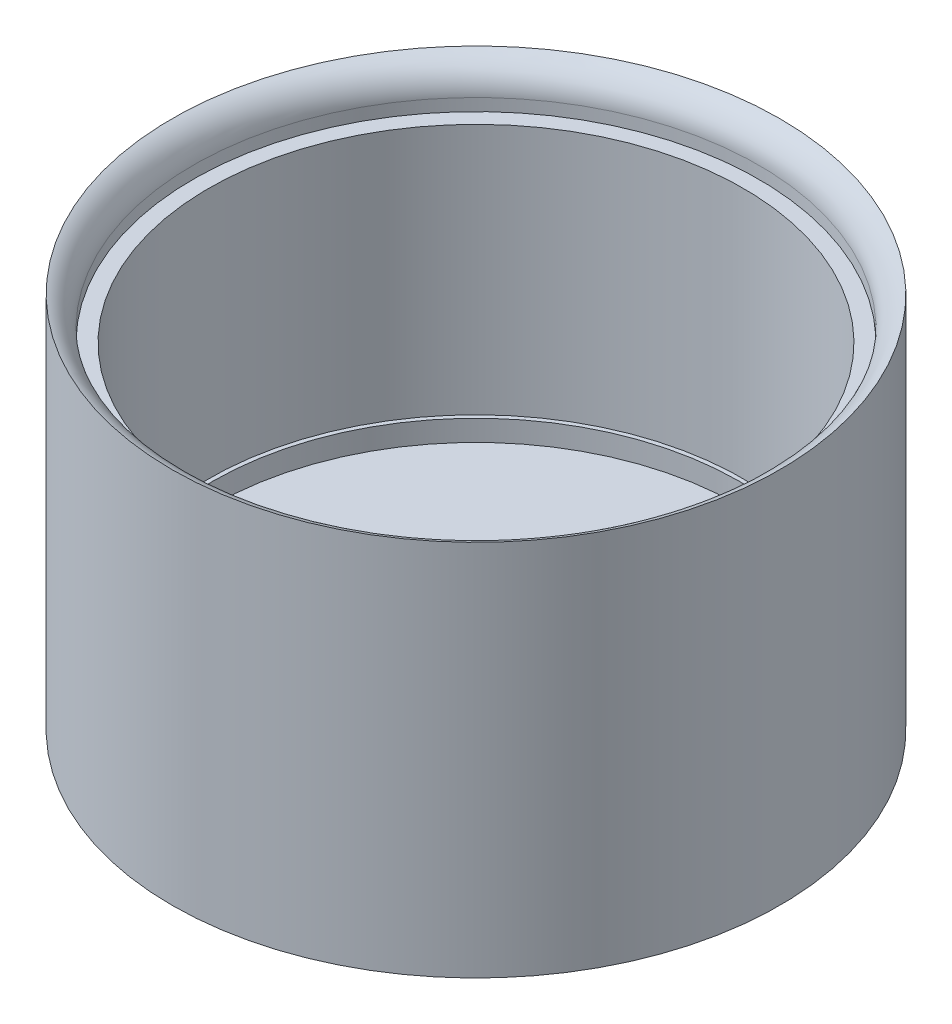
SolidWorks part; units mm, degrees
ref_plane "Alzado" through (0, 0, 0) normal (0, 0, 1) x (1, 0, 0)
ref_plane "Planta" through (0, 0, 0) normal (0, 1, 0) x (1, 0, 0)
ref_plane "Vista lateral" through (0, 0, 0) normal (1, 0, 0) x (0, 0, -1)
sketch "Sketch1" plane through (0, 0, 0) normal (0, 1, 0) x (1, 0, 0)
  circle A0 centre (0, 0) radius 25.5
  circle A1 centre (0, 0) radius 29
  dimension "D1" = 51
  dimension "D2" = 3.5
extrude "Boss-Extrude1" add sketch "Sketch1" along normal blind 30
sketch "Sketch2" plane through (0, 30, 0) normal (0, 1, 0) x (1, 0, 0)
  circle A0 centre (0, 0) radius 25.5
  circle A1 centre (0, 0) radius 26.9839
extrude "Cut-Extrude1" cut sketch "Sketch2" against normal blind 4
fillet "Fillet1" radius 3 1 edges at (0, 30, 26.9839)
sketch "Sketch3" plane through (0, 0, 0) normal (0, -1, 0) x (1, 0, 0)
  circle A0 centre (0, 0) radius 29
extrude "Boss-Extrude2" add sketch "Sketch3" along normal blind 6
sketch "Sketch4" plane through (0, 0, 0) normal (0, 1, 0) x (1, 0, 0)
  circle A2 centre (0, 0) radius 4
  dimension "D1" = 8
extrude "Cut-Extrude2" cut sketch "Sketch4" against normal blind 4.3
sketch "Sketch5" plane through (0, 0, 0) normal (0, 1, 0) x (1, 0, 0)
  circle A0 centre (0, 0) radius 25.5
  circle A1 centre (0, 0) radius 25.1
  dimension "D1" = 51
  dimension "D2" = 0.4
extrude "Boss-Extrude3" add sketch "Sketch5" along normal blind 2
